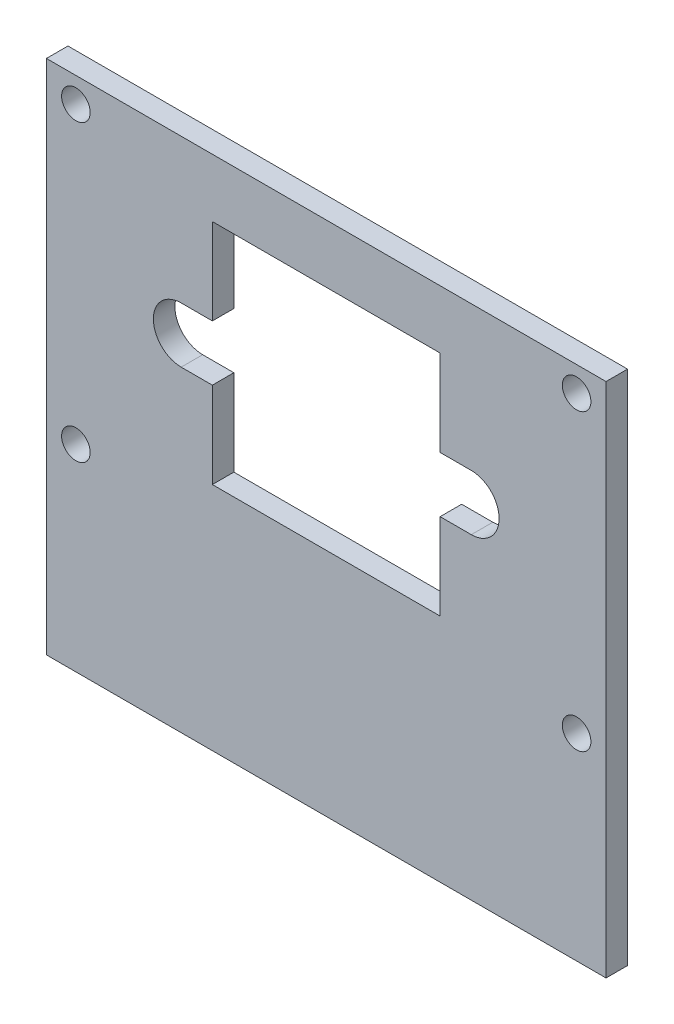
SolidWorks part; units mm, degrees
material "Beech"
ref_plane "Front Plane" through (0, 0, 0) normal (0, 0, 1) x (1, 0, 0)
ref_plane "Top Plane" through (0, 0, 0) normal (0, 1, 0) x (1, 0, 0)
ref_plane "Right Plane" through (0, 0, 0) normal (1, 0, 0) x (0, 0, -1)
sketch "Sketch1" plane through (0, 0, 0) normal (0, 0, 1) x (1, 0, 0)
  line L0 (-20.6375, 0) -> (20.6375, 0)
  line L44 (0, 14.605) -> (0, 24.13) construction
  line L45 (-8.4, 23.35) -> (-8.4, 17)
  line L46 (-20.6375, 0) -> (-20.6375, 38.1)
  line L47 (-20.6375, 38.1) -> (20.6375, 38.1)
  line L48 (20.6375, 0) -> (20.6375, 38.1)
  line L49 (-20.6375, 25.4) -> (20.6375, 25.4) construction
  line L50 (8.4, 33.8) -> (-8.4, 33.8)
  line L60 (8.4, 33.8) -> (8.4, 27.45)
  line L61 (8.4, 17) -> (-8.4, 17)
  line L62 (-8.4, 33.8) -> (-8.4, 27.45)
  line L63 (8.4, 33.8) -> (-8.4, 17) construction
  line L64 (8.4, 17) -> (-8.4, 33.8) construction
  line L66 (-8.4, 23.35) -> (-10.7, 23.35)
  line L67 (8.4, 23.35) -> (10.7, 23.35)
  line L68 (-8.4, 27.45) -> (-10.7, 27.45)
  line L69 (8.4, 27.45) -> (10.7, 27.45)
  line L71 (8.4, 23.35) -> (8.4, 17)
  arc A0 (-10.7, 23.35) -> (-10.7, 27.45) centre (-10.7, 25.4) cw
  arc A1 (10.7, 23.35) -> (10.7, 27.45) centre (10.7, 25.4) ccw
  circle A2 centre (-18.4658, 36.2585) radius 1.0541
  circle A3 centre (-18.4658, 14.5415) radius 1.0541
  circle A4 centre (18.4658, 14.5415) radius 1.0541
  circle A5 centre (18.4658, 36.2585) radius 1.0541
  point P0 (0, 0)
  point P56 (0, 25.4)
  point P60 (0, 38.1)
  dimension "D14" = 12.7
  dimension "D4" = 2.1082
  dimension "D3" = 38.1
  dimension "D12" = 41.275
  dimension "D15" = 16.8
  dimension "D19" = 16.8
  dimension "D20" = 4.1
  dimension "D21" = 2.3
  dimension "D5" = 2.1717
  dimension "D6" = 1.8415
extrude "Boss-Extrude1" add sketch "Sketch1" along normal blind 1.5875 contours L48 L47 L46 L69 region at (-20.0758, 19.05, 0)
fillet "Fillet7" [suppressed] radius 15.24
